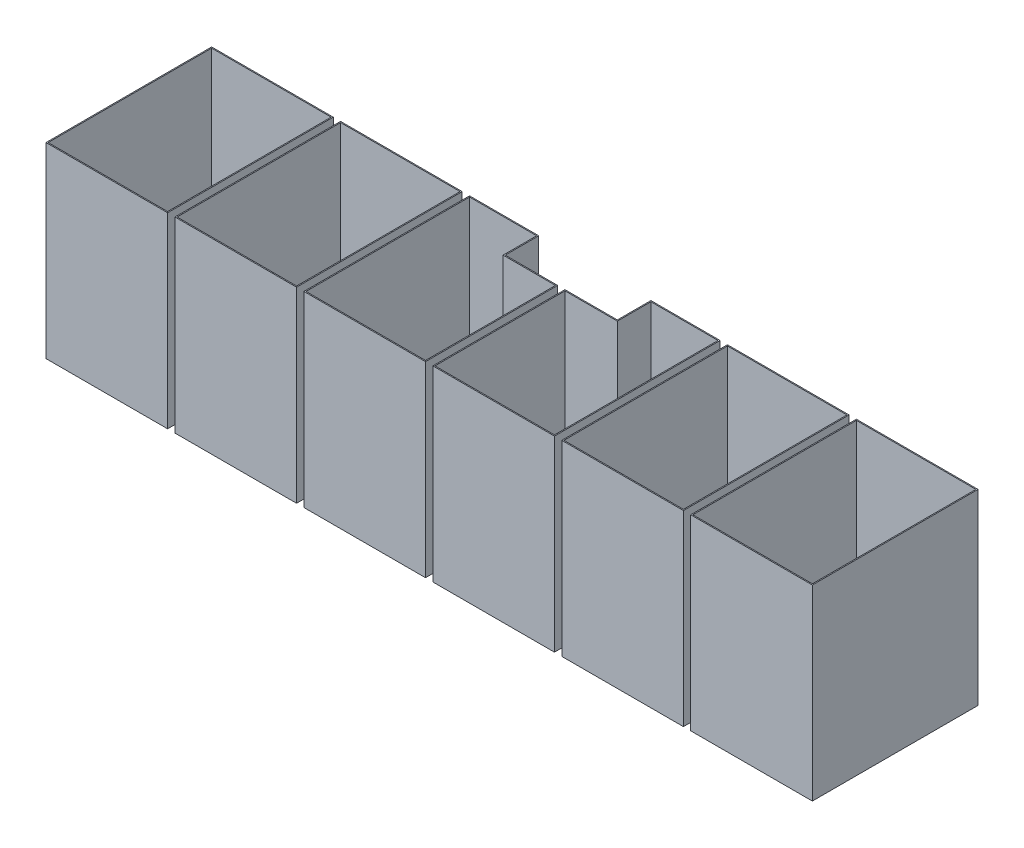
SolidWorks part; units mm, degrees
ref_plane "Front Plane" through (0, 0, 0) normal (0, 0, 1) x (1, 0, 0)
ref_plane "Top Plane" through (0, 0, 0) normal (0, 1, 0) x (1, 0, 0)
ref_plane "Right Plane" through (0, 0, 0) normal (1, 0, 0) x (0, 0, -1)
sketch "Sketch2" plane through (0, 0, 0) normal (0, 1, 0) x (1, 0, 0)
  line L4 (1612.9, 50.8) -> (3086.1, 50.8)
  line L5 (3086.1, 50.8) -> (3086.1, 2057.4)
  line L6 (3086.1, 2057.4) -> (1612.9, 2057.4)
  line L7 (1612.9, 2057.4) -> (1612.9, 50.8)
  line L8 (1612.9, 50.8) -> (3086.1, 50.8)
  line L9 (3086.1, 50.8) -> (3086.1, 2057.4)
  line L10 (3086.1, 2057.4) -> (1612.9, 2057.4)
  line L11 (1612.9, 2057.4) -> (1612.9, 50.8)
  line L12 (1524, 2057.4) -> (50.8, 2057.4)
  line L13 (50.8, 2057.4) -> (50.8, 50.8)
  line L14 (4013.2, 1651) -> (4013.2, 2057.4)
  line L15 (4648.2, 1651) -> (4013.2, 1651)
  line L16 (4648.2, 50.8) -> (4648.2, 1651)
  line L17 (3175, 50.8) -> (4648.2, 50.8)
  line L18 (3175, 2057.4) -> (3175, 50.8)
  line L19 (4013.2, 2057.4) -> (3175, 2057.4)
  line L20 (4013.2, 1651) -> (4013.2, 2057.4)
  line L21 (4648.2, 1651) -> (4013.2, 1651)
  line L22 (4648.2, 50.8) -> (4648.2, 1651)
  line L23 (3175, 50.8) -> (4648.2, 50.8)
  line L24 (3175, 2057.4) -> (3175, 50.8)
  line L25 (4013.2, 2057.4) -> (3175, 2057.4)
  line L26 (50.8, 50.8) -> (1524, 50.8)
  line L27 (1524, 50.8) -> (1524, 2057.4)
  line L28 (1524, 2057.4) -> (50.8, 2057.4)
  line L29 (50.8, 2057.4) -> (50.8, 50.8)
  line L30 (50.8, 50.8) -> (1524, 50.8)
  line L31 (1524, 50.8) -> (1524, 2057.4)
  line L32 (6299.2, 2057.4) -> (6299.2, 50.8)
  line L33 (7772.4, 2057.4) -> (6299.2, 2057.4)
  line L34 (7772.4, 50.8) -> (7772.4, 2057.4)
  line L35 (6299.2, 50.8) -> (7772.4, 50.8)
  line L36 (6299.2, 2057.4) -> (6299.2, 50.8)
  line L37 (7772.4, 2057.4) -> (6299.2, 2057.4)
  line L38 (7772.4, 50.8) -> (7772.4, 2057.4)
  line L39 (6299.2, 50.8) -> (7772.4, 50.8)
  line L40 (3073.4, 2044.7) -> (1625.6, 2044.7)
  line L41 (3073.4, 63.5) -> (3073.4, 2044.7)
  line L42 (5372.1, 2057.4) -> (5372.1, 1651)
  line L43 (6210.3, 2057.4) -> (5372.1, 2057.4)
  line L44 (6210.3, 50.8) -> (6210.3, 2057.4)
  line L45 (4737.1, 50.8) -> (6210.3, 50.8)
  line L46 (4737.1, 1651) -> (4737.1, 50.8)
  line L47 (5372.1, 1651) -> (4737.1, 1651)
  line L48 (5372.1, 2057.4) -> (5372.1, 1651)
  line L49 (6210.3, 2057.4) -> (5372.1, 2057.4)
  line L50 (6210.3, 50.8) -> (6210.3, 2057.4)
  line L51 (4737.1, 50.8) -> (6210.3, 50.8)
  line L52 (4737.1, 1651) -> (4737.1, 50.8)
  line L53 (5372.1, 1651) -> (4737.1, 1651)
  line L54 (1625.6, 63.5) -> (3073.4, 63.5)
  line L55 (1625.6, 2044.7) -> (1625.6, 63.5)
  line L56 (3073.4, 2044.7) -> (1625.6, 2044.7)
  line L57 (3073.4, 63.5) -> (3073.4, 2044.7)
  line L58 (1625.6, 63.5) -> (3073.4, 63.5)
  line L59 (1625.6, 2044.7) -> (1625.6, 63.5)
  line L60 (9334.5, 50.8) -> (9334.5, 2057.4)
  line L61 (7861.3, 50.8) -> (9334.5, 50.8)
  line L62 (7861.3, 2057.4) -> (7861.3, 50.8)
  line L63 (9334.5, 2057.4) -> (7861.3, 2057.4)
  line L64 (9334.5, 50.8) -> (9334.5, 2057.4)
  line L65 (7861.3, 50.8) -> (9334.5, 50.8)
  line L66 (7861.3, 2057.4) -> (7861.3, 50.8)
  line L67 (9334.5, 2057.4) -> (7861.3, 2057.4)
  line L68 (1511.3, 2044.7) -> (63.5, 2044.7)
  line L69 (1511.3, 63.5) -> (1511.3, 2044.7)
  line L70 (63.5, 63.5) -> (1511.3, 63.5)
  line L71 (63.5, 2044.7) -> (63.5, 63.5)
  line L72 (1511.3, 2044.7) -> (63.5, 2044.7)
  line L73 (1511.3, 63.5) -> (1511.3, 2044.7)
  line L74 (63.5, 63.5) -> (1511.3, 63.5)
  line L75 (63.5, 2044.7) -> (63.5, 63.5)
  line L76 (9321.8, 2044.7) -> (7874, 2044.7)
  line L77 (9321.8, 63.5) -> (9321.8, 2044.7)
  line L78 (7874, 63.5) -> (9321.8, 63.5)
  line L79 (7874, 2044.7) -> (7874, 63.5)
  line L80 (9321.8, 2044.7) -> (7874, 2044.7)
  line L81 (9321.8, 63.5) -> (9321.8, 2044.7)
  line L82 (7874, 63.5) -> (9321.8, 63.5)
  line L83 (7874, 2044.7) -> (7874, 63.5)
  line L84 (7759.7, 2044.7) -> (6311.9, 2044.7)
  line L85 (7759.7, 63.5) -> (7759.7, 2044.7)
  line L86 (6311.9, 63.5) -> (7759.7, 63.5)
  line L87 (6311.9, 2044.7) -> (6311.9, 63.5)
  line L88 (7759.7, 2044.7) -> (6311.9, 2044.7)
  line L89 (7759.7, 63.5) -> (7759.7, 2044.7)
  line L90 (6311.9, 63.5) -> (7759.7, 63.5)
  line L91 (6311.9, 2044.7) -> (6311.9, 63.5)
  line L94 (5384.8, 1638.3) -> (4749.8, 1638.3)
  line L95 (5384.8, 2044.7) -> (5384.8, 1638.3)
  line L96 (6197.6, 2044.7) -> (5384.8, 2044.7)
  line L97 (6197.6, 63.5) -> (6197.6, 2044.7)
  line L98 (4749.8, 63.5) -> (6197.6, 63.5)
  line L99 (4749.8, 1638.3) -> (4749.8, 63.5)
  line L100 (5384.8, 1638.3) -> (4749.8, 1638.3)
  line L101 (5384.8, 2044.7) -> (5384.8, 1638.3)
  line L102 (6197.6, 2044.7) -> (5384.8, 2044.7)
  line L103 (6197.6, 63.5) -> (6197.6, 2044.7)
  line L104 (4749.8, 63.5) -> (6197.6, 63.5)
  line L105 (4749.8, 1638.3) -> (4749.8, 63.5)
  line L106 (3187.7, 63.5) -> (4635.5, 63.5)
  line L107 (3187.7, 2044.7) -> (3187.7, 63.5)
  line L108 (4000.5, 2044.7) -> (3187.7, 2044.7)
  line L109 (4000.5, 1638.3) -> (4000.5, 2044.7)
  line L110 (4635.5, 1638.3) -> (4000.5, 1638.3)
  line L111 (4635.5, 63.5) -> (4635.5, 1638.3)
  line L112 (3187.7, 63.5) -> (4635.5, 63.5)
  line L113 (3187.7, 2044.7) -> (3187.7, 63.5)
  line L114 (4000.5, 2044.7) -> (3187.7, 2044.7)
  line L115 (4000.5, 1638.3) -> (4000.5, 2044.7)
  line L116 (4635.5, 1638.3) -> (4000.5, 1638.3)
  line L117 (4635.5, 63.5) -> (4635.5, 1638.3)
  dimension "D1" = 0
  dimension "D2" = 0
  dimension "D3" = 0
  dimension "D4" = 0
  dimension "D5" = 0
  dimension "D6" = 0
  dimension "D7" = 0
  dimension "D8" = 0
  dimension "D9" = 0
  dimension "D10" = 0
  dimension "D11" = 0
  dimension "D12" = 0
extrude "Boss-Extrude1" add sketch "Sketch2" along normal up to surface (2266.95 mm away)
